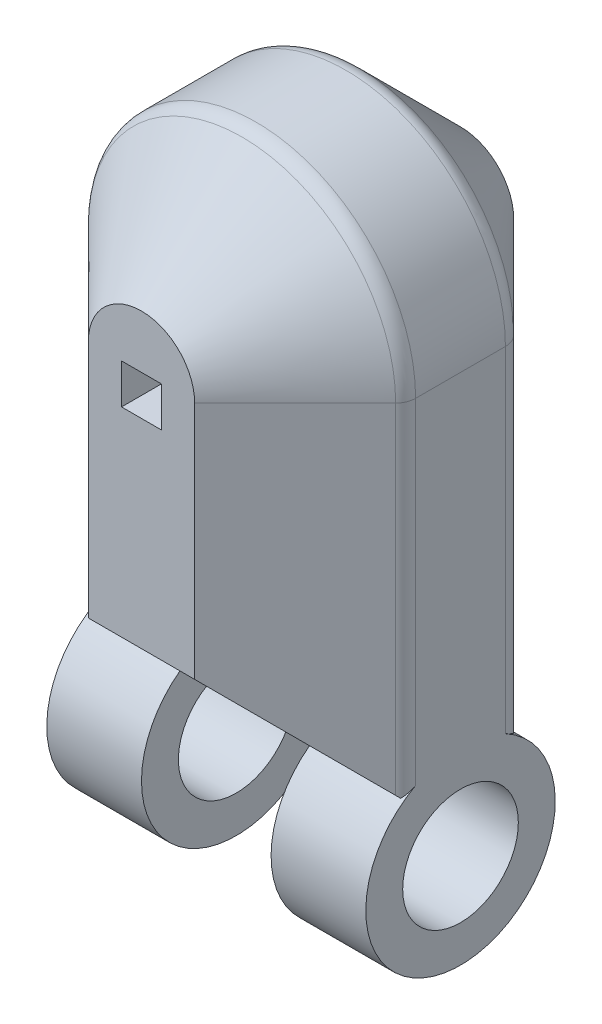
SolidWorks part; units mm, degrees
ref_plane "Front Plane" through (0, 0, 0) normal (0, 0, 1) x (1, 0, 0)
ref_plane "Top Plane" through (0, 0, 0) normal (0, 1, 0) x (1, 0, 0)
ref_plane "Right Plane" through (0, 0, 0) normal (1, 0, 0) x (0, 0, -1)
sketch "Sketch1" plane through (0, 0, 0) normal (0, 1, 0) x (1, 0, 0)
  line L0 (-1.3333, -4) -> (1.3333, -4)
  line L1 (1.3333, -4) -> (4, -1.3333)
  line L2 (4, -1.3333) -> (4, 1.3333)
  line L3 (4, 1.3333) -> (1.3333, 4)
  line L4 (1.3333, 4) -> (-1.3333, 4)
  line L5 (-1.3333, 4) -> (-4, 1.3333)
  line L6 (-4, 1.3333) -> (-4, -1.3333)
  line L7 (-4, -1.3333) -> (-1.3333, -4)
  point P16 (4, 0)
  point P19 (0, -4)
  dimension "D1" = 135
  dimension "D2" = 8
  dimension "D3" = 8
  dimension "D4" = 2.6667
extrude "Boss-Extrude1" add sketch "Sketch1" along normal blind 10
sketch "Sketch2" plane through (0, 0, 0) normal (1, 0, 0) x (0, 0, -1)
  line L3 (-4, 10) -> (-4, 0) construction
  line L5 (0, 0) -> (-4, 0)
  line L6 (-1.3333, 0) -> (1.3333, 0) construction
  line L7 (-4, 0) -> (-4, 4)
  line L8 (-4, 4) -> (0, 0)
  dimension "D2" = 45
extrude "Cut-Extrude1" cut sketch "Sketch2" against normal through all both and the other way through all contours L8 L5 L7
sketch "Sketch3" plane through (0, 0, 0) normal (0, 1, 0) x (1, 0, 0)
  line L0 (0, -3) -> (-0.5, -2.5)
  line L1 (-0.5, -2.5) -> (-0.5, -2)
  line L2 (-0.5, -2) -> (0.5, -2)
  line L3 (0.5, -2) -> (0.5, -2.5)
  line L4 (0.5, -2.5) -> (0, -3)
  line L6 (0.5, 3) -> (0.5, 2.5)
  line L7 (-0.5, 3) -> (0.5, 3)
  line L8 (-0.5, 2.5) -> (-0.5, 3)
  line L9 (0, 2) -> (-0.5, 2.5)
  line L10 (0.5, 2.5) -> (0, 2)
  line L11 (1.3333, 4) -> (-1.3333, 4) construction
  line L12 (-1.3333, -4) -> (1.3333, -4) construction
  point P6 (0, -2)
  point P13 (0, -4)
  dimension "D1" = 1
  dimension "D2" = 0.5
  dimension "D3" = 0.5
  dimension "D4" = 0.5
  dimension "D5" = 1
  dimension "D6" = 2
  dimension "D7" = 1
extrude "Cut-Extrude2" cut sketch "Sketch3" along normal blind 10
sketch "Sketch6" plane through (0, 0, 0) normal (1, 0, 0) x (0, 0, -1)
  circle A0 centre (0, -0.5) radius 2.625
  dimension "D2" = 5.25
  dimension "D1" = 0.5
extrude "Cut-Extrude4" cut sketch "Sketch6" against normal mid plane 3.25
sketch "Sketch7" plane through (-1.625, 0, 0) normal (1, 0, 0) x (0, 0, -1)
  circle A0 centre (0, -0.5) radius 2.375
  dimension "D2" = 4.75
  dimension "D1" = 0.5
extrude "Boss-Extrude3" add sketch "Sketch7" against normal up to surface (2.375 mm away) up to face at (-4, 4.2667, 0)
sketch "Sketch8" plane through (1.625, 0, 0) normal (-1, 0, 0) x (0, 0, 1)
  circle A0 centre (0, -0.5) radius 2.375
  dimension "D2" = 4.75
  dimension "D1" = 0.5
extrude "Boss-Extrude4" add sketch "Sketch8" against normal up to surface (2.375 mm away) up to face at (4, 4.2667, 0)
sketch "Sketch11" plane through (4, 0, 0) normal (1, 0, 0) x (0, 0, -1)
  circle A0 centre (0, -0.5) radius 1.45
  dimension "D1" = 2.9
extrude "Cut-Extrude6" cut sketch "Sketch11" against normal through all both and the other way through all
sketch "Sketch12" plane through (0, 10, 0) normal (0, 1, 0) x (1, 0, 0)
  line L0 (0, 4) -> (-1.3333, 4)
  line L1 (1.3333, 4) -> (-1.3333, 4) construction
  line L2 (-1.3333, 4) -> (-4, 1.3333)
  line L3 (-4, 1.3333) -> (-4, -1.3333)
  line L4 (-4, -1.3333) -> (-1.3333, -4)
  line L5 (-1.3333, -4) -> (0, -4)
  line L6 (-1.3333, -4) -> (1.3333, -4) construction
  line L7 (0, -4) -> (0, 4)
revolve "Revolve1" add sketch "Sketch12" angle 180 about L7
fillet "Fillet1" radius 0.5 3 edges at (4, 5.7327, 1.3333) (-4, 5.7327, 1.3333) (0, 14, 1.3333)
fillet "Fillet2" radius 0.5 3 edges at (4, 5.7327, -1.3333) (-4, 5.7327, -1.3333) (0, 14, -1.3333)
sketch "Sketch13" plane through (0, 0, 2) normal (0, 0, 1) x (1, 0, 0)
  line L1 (0.5, 10) -> (-0.5, 10)
  line L2 (0.5, 10) -> (0.5, 9)
  line L3 (0.5, 9) -> (-0.5, 9)
  line L4 (-0.5, 10) -> (-0.5, 9)
  line L5 (0.5, 10) -> (-0.5, 10) construction
  point P4 (0, 9)
  dimension "D1" = 1
  dimension "D2" = 1
extrude "Cut-Extrude7" cut sketch "Sketch13" along normal through all
sketch "Sketch14" plane through (0, 0, -3) normal (0, 0, 1) x (1, 0, 0)
  line L1 (0.5, 9) -> (-0.5, 9)
  line L2 (0.5, 9) -> (0.5, 10)
  line L3 (0.5, 10) -> (-0.5, 10)
  line L4 (-0.5, 9) -> (-0.5, 10)
  line L5 (0.5, 10) -> (-0.5, 10) construction
  point P4 (0, 9)
  dimension "D1" = 1
  dimension "D2" = 1
extrude "Cut-Extrude8" cut sketch "Sketch14" against normal through all
